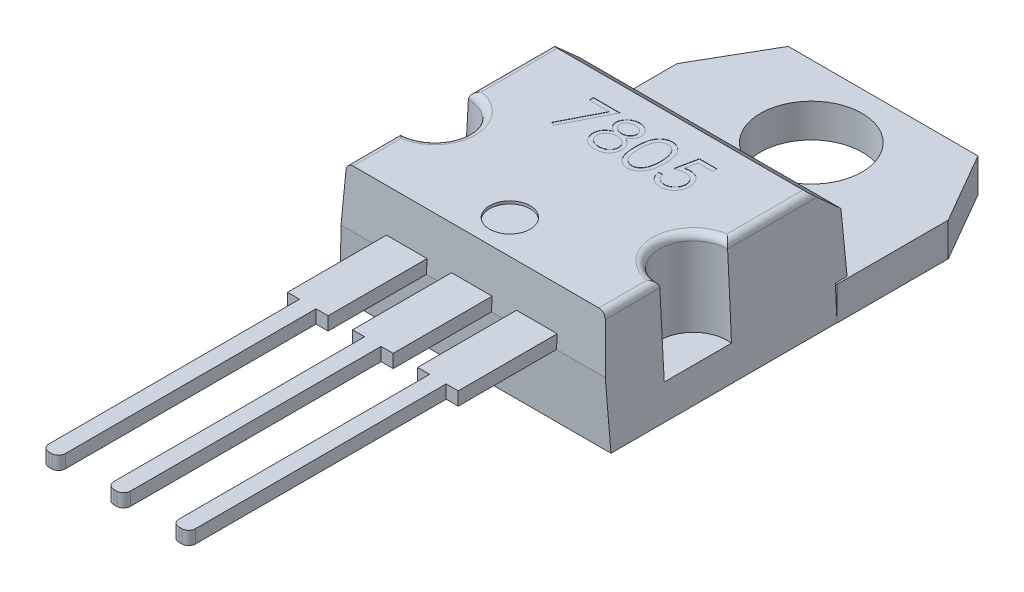
SolidWorks part; units mm, degrees
other "Camera1"
ref_plane "Front Plane" through (0, 0, 0) normal (0, 0, 1) x (1, 0, 0)
ref_plane "Top Plane" through (0, 0, 0) normal (0, 1, 0) x (1, 0, 0)
ref_plane "Right Plane" through (0, 0, 0) normal (1, 0, 0) x (0, 0, -1)
sketch "Sketch1" plane through (0, 0, 0) normal (0, 1, 0) x (1, 0, 0)
  line L1 (0, 0) -> (10, 0)
  line L2 (0, 0) -> (0, 9.05)
  line L3 (0, 9.05) -> (10, 9.05)
  line L4 (10, 0) -> (10, 9.05)
  dimension "D1" = 9.05
  dimension "D2" = 10
extrude "Boss-Extrude1" add sketch "Sketch1" along normal blind 4.4 draft 3
chamfer "Chamfer2" distance 1 angle 45 1 edges at (5, 4.4, -8.8194)
sketch "Sketch2" plane through (0, 4.4, 0) normal (0, 1, 0) x (1, 0, 0)
  line L0 (0.2306, 3.4806) -> (9.7694, 3.4806) construction
  line L1 (0.2306, 7.7627) -> (0.2306, 0.2306) construction
  line L2 (9.7694, 0.2306) -> (9.7694, 7.7627) construction
  line L3 (0.2306, 0.2306) -> (9.7694, 0.2306) construction
  line L4 (5, 3.4806) -> (5, 0.2306) construction
  circle A0 centre (0.2306, 3.4806) radius 1.25
  circle A1 centre (9.7694, 3.4806) radius 1.25
  dimension "D2" = 2.5
  dimension "D1" = 3.25
extrude "Cut-Extrude1" cut sketch "Sketch2" against normal blind 3.17
fillet "Fillet1" radius 0.25 6 edges at (9.7694, 4.4, -6.2466) (8.5194, 4.4, -3.4806) (9.7694, 4.4, -1.2306) (0.2306, 4.4, -1.2306) (1.4806, 4.4, -3.4806) (0.2306, 4.4, -6.2466)
sketch "Sketch3" plane through (0, 4.4, 0) normal (0, 1, 0) x (1, 0, 0)
  line L0 (5, 0.2306) -> (5, 1.4806) construction
  line L1 (0.4678, 0.2306) -> (9.5322, 0.2306) construction
  circle A0 centre (5, 1.4806) radius 0.75
  dimension "D2" = 1.5
  dimension "D1" = 1.25
extrude "Cut-Extrude2" cut sketch "Sketch3" against normal blind 0.1
chamfer "Chamfer3" distance 2.4 angle 5 1 edges at (5, 0, 0)
sketch "Sketch5" plane through (0, 0, 0) normal (0, 0, 1) x (1, 0, 0)
  line L0 (1.775, 2.8867) -> (3.275, 2.8867)
  line L1 (1.775, 2.8867) -> (1.775, 2.3967)
  line L2 (1.775, 2.3967) -> (3.275, 2.3967)
  line L3 (3.275, 2.8867) -> (3.275, 2.3967)
  dimension "D1" = 1.5
  dimension "D2" = 0.49
  dimension "D3" = 1.775
extrude "Boss-Extrude3" add sketch "Sketch5" along normal blind 3.5 and the other way up to next separate body
pattern_linear "LPattern2" count 3 spacing 2.4 along (1, 0, 0) of "Boss-Extrude3"
sketch "Sketch6" plane through (0, 0, 3.5) normal (0, 0, 1) x (1, 0, 0)
  line L4 (2.22, 2.8867) -> (2.22, 2.3967)
  line L5 (2.83, 2.3967) -> (2.83, 2.8867)
  line L6 (2.525, 2.8867) -> (2.525, 2.3967) construction
  line L8 (1.775, 2.8867) -> (1.775, 2.3967)
  line L9 (1.775, 2.3967) -> (3.275, 2.3967)
  line L10 (3.275, 2.3967) -> (3.275, 2.8867)
  line L11 (3.275, 2.8867) -> (1.775, 2.8867)
  line L12 (1.775, 2.8867) -> (1.775, 2.3967)
  line L13 (1.775, 2.3967) -> (3.275, 2.3967)
  line L14 (3.275, 2.3967) -> (3.275, 2.8867)
  line L15 (3.275, 2.8867) -> (1.775, 2.8867)
  line M13 (1.775, 2.3967) -> (3.275, 2.3967)
  line M15 (3.275, 2.8867) -> (1.775, 2.8867)
  dimension "D2" = 0.305
  dimension "D3" = 0.305
  dimension "D1" = 0
extrude "Boss-Extrude4" add sketch "Sketch6" along normal blind 9.5 contours L6 L13 L5 M15 | L6 L15 L4 M13
pattern_linear "LPattern4" count 3 spacing 2.4 along (1, 0, 0) of "Boss-Extrude4"
fillet "Fillet2" radius 0.25 2 edges at (2.22, 2.6417, 13) (2.83, 2.6417, 13)
fillet "Fillet3" radius 0.25 2 edges at (5.23, 2.6417, 13) (4.62, 2.6417, 13)
fillet "Fillet4" radius 0.25 2 edges at (7.63, 2.6417, 13) (7.02, 2.6417, 13)
sketch "Sketch7" plane through (0, 0, 0) normal (0, -1, 0) x (1, 0, 0)
  line L0 (10, -0.2093) -> (0, -0.2093) construction
  line L1 (1, -2.7093) -> (9, -2.7093)
  line L2 (1, -2.7093) -> (1, -8.55)
  line L3 (5, -15.25) -> (5, -9.05) construction
  line L4 (9, -2.7093) -> (9, -8.55)
  line L5 (10, -0.2093) -> (10, -9.05) construction
  line L6 (0, -9.05) -> (0, -0.2093) construction
  line L8 (10, -9.05) -> (0, -9.05) construction
  line L9 (0, -9.05) -> (0, -15.25)
  line L10 (0, -15.25) -> (10, -15.25)
  line L11 (10, -9.05) -> (10, -15.25)
  line L13 (0, -9.05) -> (0, -8.55)
  line L14 (0, -8.55) -> (1, -8.55)
  line L15 (9, -8.55) -> (10, -8.55)
  line L16 (10, -8.55) -> (10, -9.05)
  circle A0 centre (5, -12.6) radius 1.875
  dimension "D5" = 2.65
  dimension "D6" = 3.75
  dimension "D1" = 2.5
  dimension "D2" = 1
  dimension "D3" = 1
  dimension "D4" = 6.2
  dimension "D7" = 0.5
extrude "Boss-Extrude5" add sketch "Sketch7" against normal blind 1.23 and the other way blind 0.01
chamfer "Chamfer6" distance 1.5 angle 60 1 edges at (0, 0.61, -15.25)
chamfer "Chamfer7" distance 1.5 angle 60 1 edges at (10, 0.61, -15.25)
sketch "Sketch8" plane through (0, 4.4, 0) normal (0, 1, 0) x (1, 0, 0)
  text T0 "7805" font "Century Gothic" height in points 6
extrude "Cut-Extrude3" cut sketch "Sketch8" against normal blind 0.01
